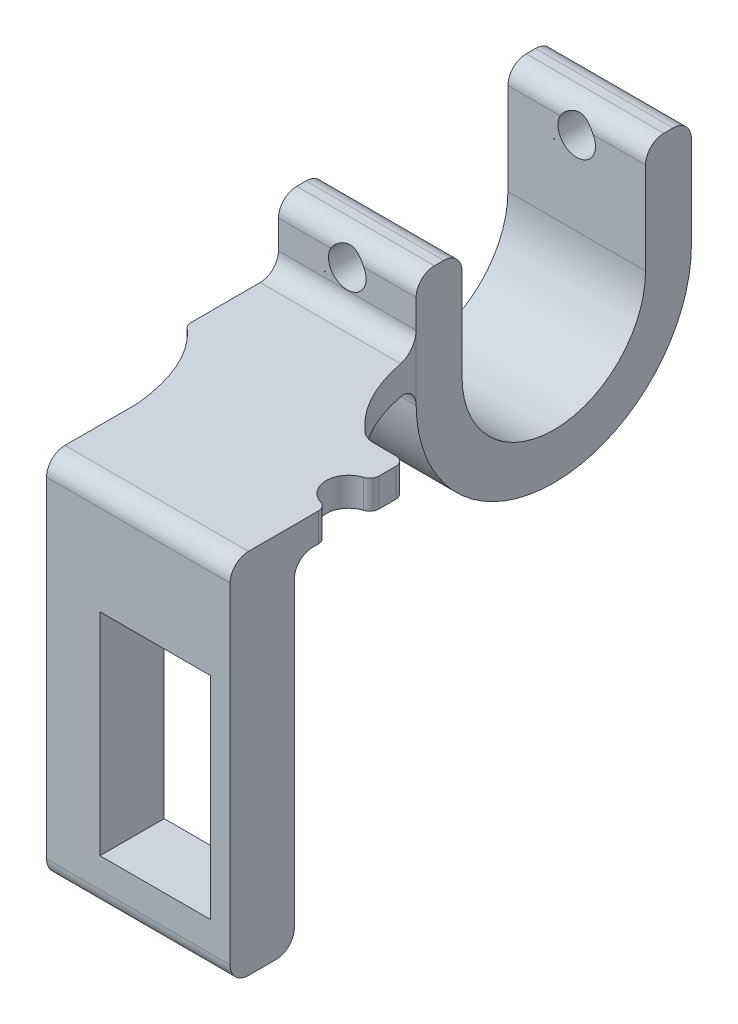
SolidWorks part; units mm, degrees
ref_plane "Front Plane" through (0, 0, 0) normal (0, 0, 1) x (1, 0, 0)
ref_plane "Top Plane" through (0, 0, 0) normal (0, 1, 0) x (1, 0, 0)
ref_plane "Right Plane" through (0, 0, 0) normal (1, 0, 0) x (0, 0, -1)
sketch "Sketch2" plane through (0, 0, 0) normal (1, 0, 0) x (0, 0, -1)
  line L0 (-38.4658, 20.7299) -> (-38.4658, 32.7299)
  line L1 (-27.3688, 20.7299) -> (-8.4658, 20.7299) construction
  line L2 (-8.4658, 20.7299) -> (-8.4658, 32.7299)
  line L3 (-13.4658, 20.7299) -> (-13.4658, 32.7299)
  line L4 (-33.4658, 20.7299) -> (-33.4658, 32.7299)
  line L5 (-38.4658, 32.7299) -> (-33.4658, 32.7299)
  line L6 (-13.4658, 32.7299) -> (-8.4658, 32.7299)
  arc A0 (-8.4658, 20.7299) -> (-38.4658, 20.7299) centre (-23.4658, 20.7299) cw
  arc A1 (-13.4658, 20.7299) -> (-33.4658, 20.7299) centre (-23.4658, 20.7299) cw
  dimension "D1" = 5
extrude "Boss-Extrude1" add sketch "Sketch2" along normal blind 15
sketch "Sketch3" plane through (0, 0, 38.4658) normal (0, 0, 1) x (1, 0, 0)
  line L0 (0, 32.7299) -> (0, 20.7299) construction
  line L1 (0, 26.7299) -> (15.7245, 26.7299) construction
  line L2 (15, 32.7299) -> (0, 32.7299) construction
  line L3 (7.5, 32.7299) -> (7.5, 20.7299) construction
  line L4 (15, 20.7299) -> (0, 20.7299) construction
  circle A0 centre (5.031, 28.2102) radius 0.0377
  circle A1 centre (7.5, 29.754) radius 2.05
extrude "Cut-Extrude1" cut sketch "Sketch3" against normal blind 39 and the other way blind 13
sketch "Sketch5" plane through (0, 0, 38.4658) normal (0, 0, 1) x (1, 0, 0)
  line L0 (0, 25.6382) -> (15, 25.6382)
  line L1 (0, 32.7299) -> (0, 20.7299) construction
  line L2 (15, 32.7299) -> (15, 20.7299) construction
  line L3 (15, 25.6382) -> (15, 22.5206)
  line L4 (15, 22.5206) -> (0, 22.5206)
  line L5 (0, 22.5206) -> (0, 25.6382)
extrude "Boss-Extrude2" add sketch "Sketch5" along normal blind 10
sketch "Sketch6" plane through (0, 0, 48.4658) normal (0, 0, 1) x (1, 0, 0)
  line L0 (15, 25.6382) -> (0, 25.6382) construction
  line L1 (4.7288, 25.6382) -> (24.7288, 25.6382)
  line L2 (4.7288, 25.6382) -> (4.7288, -14.3618)
  line L3 (4.7288, -14.3618) -> (24.7288, -14.3618)
  line L4 (24.7288, 25.6382) -> (24.7288, -14.3618)
extrude "Boss-Extrude3" add sketch "Sketch6" along normal blind 10
sketch "Sketch7" plane through (0, 0, 48.4658) normal (0, 0, -1) x (-1, 0, 0)
  line L1 (-22.5681, 13.8441) -> (-10.5481, 13.8441)
  line L2 (-22.5681, 13.8441) -> (-22.5681, -9.1759)
  line L3 (-22.5681, -9.1759) -> (-10.5481, -9.1759)
  line L4 (-10.5481, 13.8441) -> (-10.5481, -9.1759)
extrude "Cut-Extrude2" cut sketch "Sketch7" against normal through all
sketch "Sketch9" plane through (0, 22.5206, 0) normal (0, -1, 0) x (1, 0, 0)
  line L0 (4.7288, 48.4658) -> (24.7288, 48.4658) construction
  line L1 (15, 38.4658) -> (15, 48.4658)
  line L2 (15, 48.4658) -> (19.4207, 48.4658)
  line L3 (0, 48.4658) -> (4.7288, 48.4658)
  line L4 (4.7288, 48.4658) -> (4.7288, 58.4658)
  spline S0 degree 2 poles (0, 48.4658) (3.9612, 51.6766) (4.7288, 58.4658) knots 0 0 0 1 1 1
  spline S1 degree 2 poles (15, 38.4658) (15.769, 45.0857) (19.4207, 48.4658) knots 0 0 0 1 1 1
extrude "Boss-Extrude6" add sketch "Sketch9" against normal up to surface (3.1176 mm away) up to face at (11.1144, 25.6382, 48.4658)
sketch "Sketch10" plane through (4.7288, 0, 0) normal (-1, 0, 0) x (0, 0, 1)
  line L1 (48.4658, 22.5206) -> (53.4658, 22.5206)
  line L2 (48.4658, 22.5206) -> (48.4658, -15.5532)
  line L3 (48.4658, -15.5532) -> (53.4658, -15.5532)
  line L4 (53.4658, 22.5206) -> (53.4658, -15.5532)
extrude "Cut-Extrude3" cut sketch "Sketch10" against normal through all
sketch "Sketch11" plane through (4.7288, 0, 0) normal (-1, 0, 0) x (0, 0, 1)
  line L1 (58.4658, 25.6382) -> (68.4658, 25.6382)
  line L2 (58.4658, 25.6382) -> (58.4658, -14.3884)
  line L3 (58.4658, -14.3884) -> (68.4658, -14.3884)
  line L4 (68.4658, 25.6382) -> (68.4658, -14.3884)
extrude "Boss-Extrude7" add sketch "Sketch11" against normal up to surface (20 mm away) up to face at (24.7288, 11.2657, 53.4658)
sketch "Sketch12" plane through (0, 0, 58.4658) normal (0, 0, -1) x (-1, 0, 0)
  line L1 (-22.5681, 13.8441) -> (-10.5481, 13.8441)
  line L2 (-22.5681, 13.8441) -> (-22.5681, -9.1759)
  line L3 (-22.5681, -9.1759) -> (-10.5481, -9.1759)
  line L4 (-10.5481, 13.8441) -> (-10.5481, -9.1759)
extrude "Cut-Extrude4" cut sketch "Sketch12" against normal through all
sketch "Sketch13" plane through (0, -14.3884, 0) normal (0, -1, 0) x (1, 0, 0)
  line L1 (4.7288, 58.4658) -> (24.7288, 58.4658)
  line L2 (4.7288, 58.4658) -> (4.7288, 53.4658)
  line L3 (4.7288, 53.4658) -> (24.7288, 53.4658)
  line L4 (24.7288, 58.4658) -> (24.7288, 53.4658)
extrude "Cut-Extrude5" cut sketch "Sketch13" against normal up to surface (36.909 mm away) up to face at (11.6862, 22.5206, 48.1533)
sketch "Sketch14" plane through (0, -14.3884, 0) normal (0, -1, 0) x (1, 0, 0)
  line L0 (4.7288, 58.4658) -> (4.7288, 68.4658) construction
  line L1 (4.7288, 61.4677) -> (24.7288, 61.4677)
  line L2 (4.7288, 61.4677) -> (4.7288, 58.4658)
  line L3 (4.7288, 58.4658) -> (24.7288, 58.4658)
  line L4 (24.7288, 61.4677) -> (24.7288, 58.4658)
extrude "Cut-Extrude6" cut sketch "Sketch14" against normal up to surface (36.909 mm away) up to face at (14.1087, 22.5206, 48.4658)
sketch "Sketch15" plane through (0, 25.6382, 0) normal (0, 1, 0) x (1, 0, 0)
  line L1 (24.7288, -68.4658) -> (24.7288, -48.4658) construction
  line L2 (24.7288, -53.1004) -> (24.7288, -57.9909)
  arc A1 (24.7288, -53.1004) -> (24.7288, -57.9909) centre (24.7288, -55.5456) ccw
extrude "Cut-Extrude8" cut sketch "Sketch15" against normal through all
sketch "Sketch16" plane through (0, 25.6382, 0) normal (0, 1, 0) x (1, 0, 0)
  line L1 (19.4207, -48.4658) -> (24.7921, -48.4658)
  line L2 (19.4207, -48.4658) -> (19.4207, -49.4134)
  line L3 (19.4207, -49.4134) -> (24.7921, -49.4134)
  line L4 (24.7921, -48.4658) -> (24.7921, -49.4134)
extrude "Cut-Extrude9" cut sketch "Sketch16" against normal through all
sketch "Sketch17" plane through (0, 25.6382, 0) normal (0, 1, 0) x (1, 0, 0)
  line L0 (19.4207, -49.4134) -> (24.7288, -49.4134) construction
  line L9 (24.7288, -49.4134) -> (19.4207, -49.4134)
  line L10 (19.4207, -49.4134) -> (19.4207, -48.4658)
  line L11 (15, -38.4658) -> (0, -38.4658)
  line L12 (0, -38.4658) -> (0, -48.4658)
  line L13 (4.7288, -58.4658) -> (4.7288, -68.4658)
  line L14 (4.7288, -68.4658) -> (24.7288, -68.4658)
  line L15 (24.7288, -68.4658) -> (24.7288, -57.9909)
  line L16 (24.7288, -53.1004) -> (24.7288, -49.4134)
  line L17 (24.7288, -49.4134) -> (21.3218, -49.4134)
  line L19 (15, -38.4658) -> (0, -38.4658)
  line L20 (0, -38.4658) -> (0, -48.4658)
  line L21 (4.7288, -58.4658) -> (4.7288, -68.4658)
  line L22 (4.7288, -68.4658) -> (24.7288, -68.4658)
  line L23 (24.7288, -68.4658) -> (24.7288, -57.9909)
  line L24 (24.7288, -53.1004) -> (24.7288, -49.4134)
  arc A1 (24.7288, -53.1004) -> (24.7288, -57.9909) centre (24.7288, -55.5456) ccw
  arc A2 (24.7288, -53.1004) -> (24.7288, -57.9909) centre (24.7288, -55.5456) ccw
  parabola Q2 (19.4207, -48.4658) -> (15, -38.4658) focus (23.3808, -44.3527) apex (19.5867, -48.6166)
  parabola Q3 (0, -48.4658) -> (4.7288, -58.4658) focus (-3.2098, -52.8342) apex (0.3915, -48.7988)
  parabola Q4 (19.4207, -48.4658) -> (15, -38.4658) focus (23.3808, -44.3527) apex (19.5867, -48.6166)
  parabola Q5 (0, -48.4658) -> (4.7288, -58.4658) focus (-3.2098, -52.8342) apex (0.3915, -48.7988)
  spline S0 degree 2 poles (19.4207, -48.4658) (20.2509, -49.4317) (21.3218, -49.4134) knots 0 0 0 1 1 1
  dimension "D1" = 0
extrude "Boss-Extrude8" add sketch "Sketch17" against normal up to surface (3.1176 mm away) up to face at (14.5385, 22.5206, 51.4736)
fillet "Fillet1" radius 1 5 edges at (24.7288, 24.0794, 53.1004) (24.7288, 24.0794, 57.9909) (24.7288, 24.0794, 49.4134) (0, 24.0794, 48.4658)
fillet "Fillet2" radius 2 3 edges at (7.5, 32.7299, 33.4658) (7.5, 32.7299, 38.4658) (7.5, 25.6382, 38.4658)
fillet "Fillet3" radius 2 6 edges at (14.7288, -14.3884, 61.4677) (14.7288, -14.3884, 68.4658) (14.7288, 22.5206, 61.4677) (7.5, 22.5206, 38.4658) (7.5, 32.7299, 8.4658) (7.5, 32.7299, 13.4658)
fillet "Fillet4" radius 2 1 edges at (14.7288, 25.6382, 68.4658)
